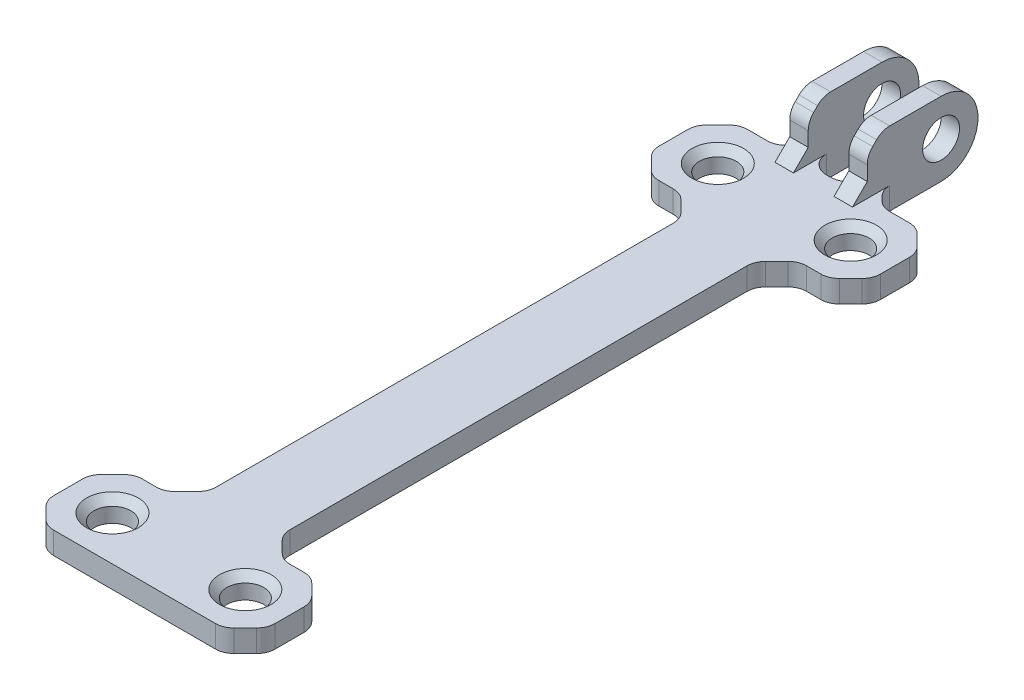
SolidWorks part; units mm, degrees
ref_plane "Front" through (0, 0, 0) normal (0, 0, 1) x (1, 0, 0)
ref_plane "Top" through (0, 0, 0) normal (0, 1, 0) x (1, 0, 0)
ref_plane "Right" through (0, 0, 0) normal (1, 0, 0) x (0, 0, -1)
sketch "Sketch2" plane through (0, 0, 0) normal (0, 1, 0) x (1, 0, 0)
  line L3 (15, 0) -> (-15, 0)
  line L7 (-15, 0) -> (-15, -12)
  line L10 (-15, -12) -> (-5, -12)
  line L11 (-5, -12) -> (-5, -82)
  line L12 (-5, -82) -> (-15, -82)
  line L13 (-15, -82) -> (-15, -94)
  line L14 (-15, -94) -> (15, -94)
  line L15 (0, 15.4924) -> (0, -70.868) construction
  line L16 (15, -82) -> (15, -94)
  line L17 (5, -82) -> (15, -82)
  line L18 (5, -12) -> (5, -82)
  line L19 (15, -12) -> (5, -12)
  line L20 (15, 0) -> (15, -12)
  circle A0 centre (-9, -6) radius 2.5
  circle A1 centre (-9, -88) radius 2.5
  circle A2 centre (9, -88) radius 2.5
  circle A3 centre (9, -6) radius 2.5
  point P12 (0, -94)
  point P18 (0, 0)
extrude "Boss-Extrude1" add sketch "Sketch2" along normal blind 3 contours L20 L3 L7 L10 L11 L12 L13 L14 L16 L17 L18 L19 A2 A1 A0 A3 region at (0, 0, 47)
sketch "Sketch3" plane through (0, 0, 0) normal (1, 0, 0) x (0, 0, -1)
  line L1 (0, 0) -> (15, 0)
  line L2 (0, 0) -> (0, 10)
  line L3 (0, 10) -> (15, 10)
  line L4 (15, 0) -> (15, 10)
  dimension "D1" = 10
  dimension "D2" = 15
extrude "Boss-Extrude2" add sketch "Sketch3" along normal blind 2.5 from offset 2.75
fillet "Fillet2" 2 edges at (4, 10, -15) (4, 0, -15) type full round first side face at (4, 10, -7.5) second side face at (9, 0, 90.5) middle face at (4, 5, -15)
mirror "Mirror1" about plane through (0, 0, 0) normal (1, 0, 0) of "Fillet2", "Boss-Extrude2"
chamfer "Chamfer1" distance 2 angle 45 2 edges at (4, 3, 0) (-4, 3, 0)
chamfer "Chamfer2" distance 2 angle 45 4 edges at (-5.25, 1.5, 0) (5.25, 1.5, 0) (4, 10, 0) (-4, 10, 0)
sketch "Sketch5" plane through (5.25, 0, 0) normal (1, 0, 0) x (0, 0, -1)
  circle A0 centre (10, 5) radius 2.5
  dimension "D1" = 5
extrude "Cut-Extrude2" cut sketch "Sketch5" against normal through all
chamfer "Chamfer3" distance 3 angle 45 12 edges at (-5, 1.5, 12) (5, 1.5, 12) (5, 1.5, 82) (-5, 1.5, 82) (-15, 1.5, 94) (15, 1.5, 94) (15, 1.5, 82) (-15, 1.5, 82) (-15, 1.5, 0) (-15, 1.5, 12) (15, 1.5, 0) (15, 1.5, 12)
fillet "Fillet3" radius 2.5 34 edges at (-15, 1.5, 85) (-12, 1.5, 82) (-8, 1.5, 82) (-5, 1.5, 79) (-5, 1.5, 15) (-8, 1.5, 12) (-12, 1.5, 12) (-15, 1.5, 9) (-12, 1.5, 0) (-7.25, 1.5, 0) (-5.25, 1.5, -2) (-2.75, 1.5, 0) (2.75, 1.5, 0) (5.25, 1.5, -2) (7.25, 1.5, 0) (12, 1.5, 0) (15, 1.5, 3) (15, 1.5, 9) (12, 1.5, 12) (8, 1.5, 12) (5, 1.5, 15) (5, 1.5, 79) (8, 1.5, 82) (12, 1.5, 82) (15, 1.5, 85) (15, 1.5, 91) (12, 1.5, 94) (-12, 1.5, 94) (-15, 1.5, 91) (-15, 1.5, 3) (4, 8, 0) (4, 10, -2) (-4, 10, -2) (-4, 8, 0)
chamfer "Chamfer4" distance 1 angle 45 4 edges at (-9, 3, 90.5) (9, 3, 90.5) (9, 3, 8.5) (-9, 3, 8.5)
equation "\"D8@Sketch2\"=\"D7@Sketch2\""
equation "\"D3@Sketch2\"=\"D7@Sketch2\""
equation "\"D2@Sketch2\"=\"D7@Sketch2\""
